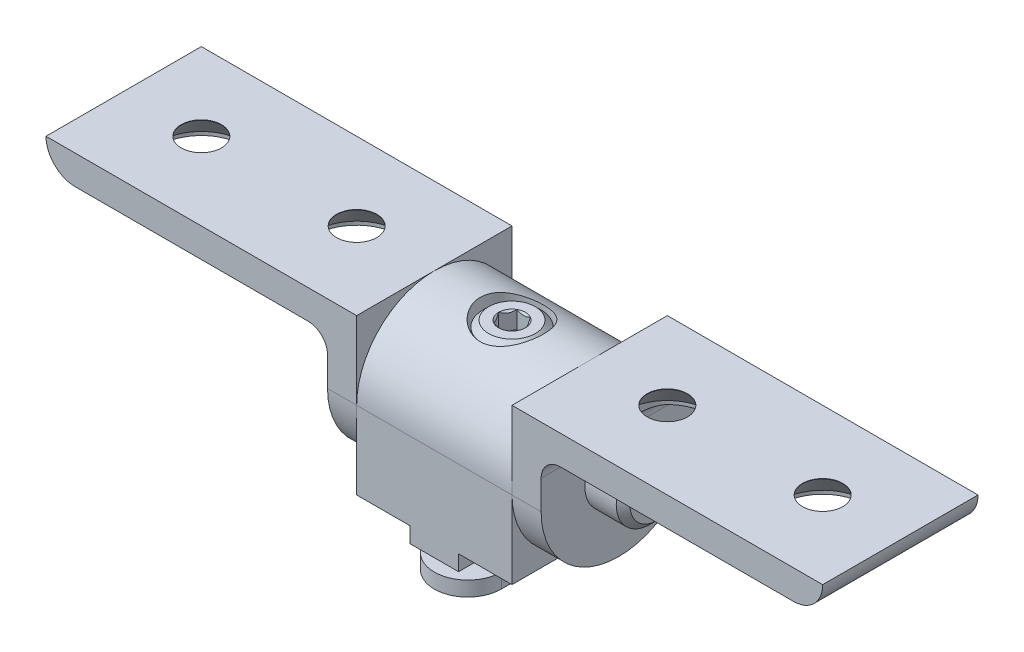
SolidWorks part; units mm, degrees
ref_plane "Front Plane" through (0, 0, 0) normal (0, 0, 1) x (1, 0, 0)
ref_plane "Top Plane" through (0, 0, 0) normal (0, 1, 0) x (1, 0, 0)
ref_plane "Right Plane" through (0, 0, 0) normal (1, 0, 0) x (0, 0, -1)
sketch "Sketch1" plane through (0, 0, 0) normal (1, 0, 0) x (0, 0, -1)
  line L0 (0, 0) -> (0, -6.985) construction
  line L2 (-12.7, 12.7) -> (-12.7, 0) construction
  line L3 (-12.7, 0) -> (12.7, 0) construction
  line L4 (12.7, 12.7) -> (12.7, 0) construction
  line L5 (-4.7625, 24.765) -> (4.7625, 24.765) construction
  line L7 (12.7, 0) -> (12.7, -2.54) construction
  line L12 (12.7, -2.54) -> (4.7752, -2.54) construction
  line L13 (-5.1911, 18.415) -> (5.1911, 18.415) construction
  line L14 (-3.2982, 12.7) -> (3.2982, 12.7) construction
  line L15 (0, 18.415) -> (0, 24.765) construction
  line L16 (-3.175, 19.5262) -> (-3.175, 18.415) construction
  line L17 (-3.175, 18.415) -> (-2.3501, 18.8912) construction
  line L18 (-2.3501, 18.8912) -> (-2.3501, 19.05) construction
  line L19 (-2.3501, 19.05) -> (-3.175, 19.5262) construction
  line L20 (-2.3501, 18.9706) -> (-3.175, 18.9706) construction
  line L21 (-3.175, 19.5262) -> (-3.3125, 19.6056) construction
  line L22 (-3.3125, 19.6056) -> (-3.3125, 18.3356) construction
  line L23 (-3.3125, 18.3356) -> (-3.175, 18.415) construction
  line L24 (-2.7626, 19.2881) -> (-2.7626, 18.6531) construction
  line L25 (-3.175, 18.9706) -> (-3.3125, 18.9706) construction
  circle A1 centre (0, 12.7) radius 3.175 construction
  circle A2 centre (0, 12.7) radius 12.7 construction
  point P6 (0, 25.4)
  point P11 (0, 18.415)
  point P20 (0, -6.985)
  point P24 (0, 18.415)
  point P25 (0, 12.7)
  point P45 (3.175, 12.7)
  dimension "D3" = 60
  dimension "D4" = 0.635
  dimension "D5" = 0.1588
sketch "Sketch6" plane through (0, 0, 0) normal (0, 0, 1) x (1, 0, 0)
  line L1 (12.7, 0) -> (-12.7, 0) construction
  line L5 (-23.7109, 18.2563) -> (-17.4625, 18.2563) construction
  line L6 (-12.7, 0) -> (-63.5, 0) construction
  line L7 (-17.4625, 18.2563) -> (-17.4625, 17.4625) construction
  line L10 (-17.4625, 17.4625) -> (-12.7, 17.4625) construction
  line L11 (-12.7, 17.4625) -> (-12.7, 15.875) construction
  line L12 (-12.7, 15.875) -> (-6.35, 15.875) construction
  line L13 (-6.35, 15.875) -> (-6.35, 9.525) construction
  line L14 (-6.35, 9.525) -> (-12.7, 9.525) construction
  line L15 (-12.7, 9.525) -> (-12.7, 7.9375) construction
  line L16 (-12.7, 7.9375) -> (-17.4625, 7.9375) construction
  line L19 (-17.4625, 7.9375) -> (-17.4625, 7.1438) construction
  line L20 (-17.4625, 7.1438) -> (-23.7109, 7.1438) construction
  line L21 (-23.7109, 7.1438) -> (-23.7109, 18.2563) construction
  line L22 (-23.7109, 12.7) -> (-6.35, 12.7) construction
  line L23 (12.7, 0) -> (63.5, 0) construction
  line L24 (-63.5, 0) -> (-63.5, 4.7625) construction
  line L25 (63.5, 0) -> (63.5, 4.7625) construction
  point P12 (0, 0)
  point P18 (-25.4, 0)
  point P23 (-50.8, 0)
  point P25 (-38.1, 0)
  dimension "D6" = 6.35
  dimension "D1" = 12.7
sketch "Sketch2" plane through (0, 0, 0) normal (1, 0, 0) x (0, 0, -1)
  line L0 (12.7, 12.7) -> (12.7, 0) construction
  line L1 (-12.7, 0) -> (12.7, 0) construction
  line L2 (-12.7, 12.7) -> (-12.7, 0) construction
  line L3 (12.7, 12.7) -> (12.7, 0)
  line L4 (-12.7, 0) -> (12.7, 0)
  line L5 (-12.7, 12.7) -> (-12.7, 0)
  circle A0 centre (0, 12.7) radius 3.175 construction
  circle A2 centre (0, 12.7) radius 3.175
  arc A4 (-12.7, 12.7) -> (12.7, 12.7) centre (0, 12.7) cw
extrude "Boss-Extrude1" add sketch "Sketch2" along normal mid plane 25.4 contours A4 L5 L4 L3 A2
sketch "Sketch3" plane through (0, 0, 0) normal (1, 0, 0) x (0, 0, -1)
  line L11 (4.7752, -2.54) -> (12.7, -2.54)
  line L12 (4.7752, -2.54) -> (4.7752, 0)
  line L13 (4.7752, 0) -> (12.7, 0)
  line L14 (12.7, -2.54) -> (12.7, 0)
  line L15 (-12.7, 0) -> (-4.7752, 0)
  line L16 (-12.7, 0) -> (-12.7, -2.54)
  line L17 (-12.7, -2.54) -> (-4.7752, -2.54)
  line L18 (-4.7752, 0) -> (-4.7752, -2.54)
  dimension "D1" = 2.54
  dimension "D2" = 7.9248
extrude "Boss-Extrude2" add sketch "Sketch3" along normal mid plane 7.9248
sketch "Sketch4" plane through (0, 0, 0) normal (0, 0, 1) x (1, 0, 0)
  line L0 (12.7, 12.7) -> (12.7, 0) construction
  line L9 (12.7, 0) -> (3.9624, 0) construction
  line L11 (4.7752, -2.54) -> (12.7, -2.54)
  line L12 (4.7752, -2.54) -> (4.7752, 0)
  line L13 (4.7752, 0) -> (12.7, 0)
  line L14 (12.7, -2.54) -> (12.7, 0)
  line L15 (-12.7, 0) -> (-4.7752, 0)
  line L16 (-12.7, 0) -> (-12.7, -2.54)
  line L17 (-12.7, -2.54) -> (-4.7752, -2.54)
  line L18 (-4.7752, 0) -> (-4.7752, -2.54)
  dimension "D1" = 7.9248
  dimension "D2" = 2.54
extrude "Boss-Extrude3" [suppressed] add sketch "Sketch4" along normal mid plane 7.9248
sketch "Sketch22" plane through (0, 0, 0) normal (0, 0, 1) x (1, 0, 0)
  line L6 (-12.7, 0) -> (-12.7, 25.4)
  line L7 (-12.7, 25.4) -> (-63.5, 25.4)
  line L9 (-58.7375, 20.6375) -> (-20.6375, 20.6375)
  line L10 (-17.4625, 17.4625) -> (-17.4625, 0)
  line L11 (-12.7, 0) -> (-63.5, 0) construction
  line L12 (-17.4625, 0) -> (-12.7, 0)
  line L13 (-20.6375, 20.6375) -> (-20.6375, 25.4) construction
  line L14 (-17.4625, 17.4625) -> (-12.7, 17.4625) construction
  line L15 (-63.5, 0) -> (-63.5, 4.7625) construction
  arc A2 (-17.4625, 17.4625) -> (-20.6375, 20.6375) centre (-20.6375, 17.4625) ccw
  arc A3 (-58.7375, 20.6375) -> (-63.5, 25.4) centre (-58.7375, 25.4) cw
  dimension "D1" = 3.175
extrude "Boss-Extrude8" add sketch "Sketch22" along normal mid plane 25.4 separate body
sketch "Sketch23" plane through (-17.4625, 0, 0) normal (-1, 0, 0) x (0, 0, 1)
  line L3 (12.7, 12.7) -> (12.7, 0) construction
  line L4 (-12.7, 12.7) -> (-12.7, -6.985)
  line L5 (-12.7, -6.985) -> (12.7, -6.985)
  line L6 (12.7, -6.985) -> (12.7, 12.7)
  circle A1 centre (0, 12.7) radius 4.7625
  arc A2 (-12.7, 12.7) -> (12.7, 12.7) centre (0, 12.7) ccw
  circle A3 centre (0, 12.7) radius 12.7 construction
extrude "Cut-Extrude7" cut sketch "Sketch23" against normal through all
sketch "Sketch24" plane through (0, 0, 0) normal (0, 0, 1) x (1, 0, 0)
  line L0 (-50.8, 0) -> (-50.8, 25.4) construction
  line L11 (-12.7, 25.4) -> (-63.5, 25.4) construction
  line L12 (-54.0982, 25.4) -> (-54.0982, 25.3319)
  line L13 (-54.0982, 25.3319) -> (-57.6821, 21.209)
  line L14 (-57.6821, 21.209) -> (-57.6821, 20.6375)
  line L15 (-58.7375, 20.6375) -> (-20.6375, 20.6375) construction
  line L16 (-57.6821, 20.6375) -> (-50.8, 20.6375) construction
  line L17 (-50.8, 20.6375) -> (-50.8, 25.4)
  line L18 (-50.8, 25.4) -> (-54.0982, 25.4)
  line L19 (-57.6821, 20.6375) -> (-57.6821, 12.7)
  line L20 (-57.6821, 12.7) -> (-50.8, 12.7)
  line L21 (-50.8, 12.7) -> (-50.8, 20.6375)
  line L22 (-23.7109, 12.7) -> (-6.35, 12.7) construction
  dimension "D1" = 49
  dimension "D2" = 6.5964
  dimension "D3" = 13.7643
  dimension "D4" = 0.5715
revolve "Cut-Revolve1" cut sketch "Sketch24" angle 360 about L0
pattern_linear "LPattern1" count 2 spacing 25.4 along (1, 0, 0) of "Cut-Revolve1"
sketch "Sketch8" plane through (0, 0, 0) normal (0, 0, 1) x (1, 0, 0)
  line L6 (-22.5996, 18.2563) -> (-17.4625, 18.2563)
  line L9 (-17.4625, 18.2563) -> (-17.4625, 17.4625)
  line L10 (-17.4625, 17.4625) -> (-12.7, 17.4625)
  line L11 (-12.7, 17.4625) -> (-12.7, 15.875)
  line L12 (-12.7, 15.875) -> (-6.35, 15.875)
  line L13 (-6.35, 15.875) -> (-6.35, 12.7)
  line L19 (-23.7109, 12.7) -> (-23.7109, 17.145)
  line L20 (-23.7109, 12.7) -> (-6.35, 12.7)
  line L21 (-23.7109, 12.7) -> (0, 12.7) construction
  line L22 (-23.7109, 17.145) -> (-22.5996, 18.2563)
  dimension "D1" = 45
  dimension "D2" = 1.1113
revolve "Revolve1" add sketch "Sketch8" angle 360 about L21
sketch "Sketch9" plane through (-23.7109, 0, 0) normal (-1, 0, 0) x (0, 0, 1)
  line L1 (0, 14.8997) -> (-1.905, 13.7999)
  line L2 (-1.905, 13.7999) -> (-1.905, 11.6001)
  line L3 (-1.905, 11.6001) -> (0, 10.5003)
  line L4 (0, 10.5003) -> (1.905, 11.6001)
  line L5 (1.905, 11.6001) -> (1.905, 13.7999)
  line L6 (1.905, 13.7999) -> (0, 14.8997)
  circle A0 centre (0, 12.7) radius 1.905 construction
extrude "Cut-Extrude1" cut sketch "Sketch9" against normal blind 2.8575
sketch "Sketch10" plane through (-23.7109, 0, 0) normal (-1, 0, 0) x (0, 0, 1)
  circle A0 centre (0, 12.7) radius 2.1997
extrude "Cut-Extrude2" cut sketch "Sketch10" against normal through all draft 45
mirror "Mirror2" about plane through (0, 0, 0) normal (1, 0, 0) of bodies 111 129 107 126
ref_plane "Plane2" through (0, 18.415, 0) normal (0, 1, 0) x (1, 0, 0)
sketch "Sketch12" plane through (0, 18.415, 0) normal (0, 1, 0) x (1, 0, 0)
  circle A0 centre (0, 0) radius 5.1911
extrude "Cut-Extrude3" cut sketch "Sketch12" along normal through all
sketch "Sketch13" plane through (0, 18.415, 0) normal (0, 1, 0) x (1, 0, 0)
  circle A0 centre (0, 0) radius 3.2982
extrude "Cut-Extrude4" cut sketch "Sketch13" against normal through all
ref_plane "Plane3" through (0, -6.985, 0) normal (0, 1, 0) x (1, 0, 0)
sketch "Sketch14" plane through (0, -6.985, 0) normal (0, 1, 0) x (1, 0, 0)
  line L0 (0, 7.2231) -> (0, -7.2231) construction
  line L1 (5.4769, 7.2231) -> (5.4769, -7.2231)
  line L2 (-5.4769, 7.2231) -> (-5.4769, -7.2231)
  arc A0 (5.4769, 7.2231) -> (-5.4769, 7.2231) centre (0, 7.2231) ccw
  arc A1 (-5.4769, -7.2231) -> (5.4769, -7.2231) centre (0, -7.2231) ccw
  circle A3 centre (0, 0) radius 3.175
  point P2 (0, 0)
  point P10 (0, -12.7)
  dimension "D1" = 6.35
  dimension "D2" = 2.3019
extrude "Boss-Extrude6" add sketch "Sketch14" along normal blind 2.413 separate body
sketch "Sketch16" plane through (0, 18.415, 0) normal (0, 1, 0) x (1, 0, 0)
  circle A0 centre (0, 0) radius 3.175
extrude "Boss-Extrude7" add sketch "Sketch16" against normal up to vertex (25.4 mm away) separate body up to point (0, -6.985, 0)
sketch "Sketch17" plane through (0, 18.415, 0) normal (0, 1, 0) x (1, 0, 0)
  circle A1 centre (0, 0) radius 3.175
  circle A2 centre (0, 0) radius 3.175
  dimension "D1" = 0
sketch "Sketch19" plane through (0, 0, 0) normal (1, 0, 0) x (0, 0, -1)
  line L0 (0, 18.415) -> (0, 24.765)
  line L1 (0, 18.415) -> (0, 24.765) construction
  line L2 (0, 24.765) -> (3.81, 24.765)
  line L3 (3.81, 24.765) -> (4.7625, 23.8125)
  line L4 (4.7625, 23.8125) -> (4.7625, 18.415)
  line L5 (-5.1911, 18.415) -> (5.1911, 18.415) construction
  line L6 (4.7625, 18.415) -> (0, 18.415)
  line L7 (0, 25.4) -> (0, 0) construction
  dimension "D1" = 45
  dimension "D2" = 0.9525
  dimension "D3" = 6.35
revolve "Revolve3" add sketch "Sketch19" angle 360 about L7
sketch "Sketch20" plane through (0, 24.765, 0) normal (0, 1, 0) x (1, 0, 0)
  line L1 (1.0999, 1.905) -> (-1.0999, 1.905)
  line L2 (-1.0999, 1.905) -> (-2.1997, 0)
  line L3 (-2.1997, 0) -> (-1.0999, -1.905)
  line L4 (-1.0999, -1.905) -> (1.0999, -1.905)
  line L5 (1.0999, -1.905) -> (2.1997, 0)
  line L6 (2.1997, 0) -> (1.0999, 1.905)
  circle A0 centre (0, 0) radius 1.905 construction
  dimension "D1" = 3.81
extrude "Cut-Extrude5" cut sketch "Sketch20" against normal blind 2.8575
sketch "Sketch21" plane through (0, 24.765, 0) normal (0, 1, 0) x (1, 0, 0)
  circle A0 centre (0, 0) radius 2.1997
extrude "Cut-Extrude6" cut sketch "Sketch21" against normal through all draft 45
curve "Helix/Spiral1" pitch 1.27 height 26.67 turns 21
sketch "Sketch18" plane through (0, 0, 0) normal (1, 0, 0) x (0, 0, -1)
  line L0 (-3.175, 19.5262) -> (-3.175, 18.415)
  line L1 (-3.175, 18.415) -> (-2.3501, 18.8912)
  line L2 (-2.3501, 18.8912) -> (-2.3501, 19.05)
  line L3 (-2.3501, 19.05) -> (-3.175, 19.5262)
sweep "Cut-Sweep1" cut profiles "Sketch18" path "Helix/Spiral1"
equation "\"D1@Boss-Extrude1\"=\"D@Sketch1\""
equation "\"D1@Boss-Extrude2\"=\"Tab Width@Sketch1\""
equation "\"D2@Sketch4\" = \"Tab Height@Sketch1\""
equation "\"D1@Sketch4\"=\"Tab Width@Sketch1\""
equation "\"D1@Boss-Extrude3\"=\"Tab Width@Sketch1\""
equation "\"D1@Sketch3\"=\"Tab Height@Sketch1\""
equation "\"D2@Sketch3\"=\"Tab Width@Sketch1\""
equation "\"D1@Cut-Extrude1\"=\"Hex Size@Sketch9\"*.75"
equation "\"Screw Clearence@Sketch1\"=\"Thread OD@Sketch1\"*1.0388"
equation "\"D1@Sketch14\"=\"Thread OD@Sketch1\""
equation "\"D4@Sketch1\"=\"Pitch@Sketch1\"/2"
equation "\"D5@Sketch1\"=\"Pitch@Sketch1\"/8"
equation "\"D4@Helix/Spiral1\"=\"Pitch@Sketch1\""
equation "\"D3@Helix/Spiral1\"=\"Thread Length@Sketch1\"+\"Pitch@Sketch1\""
equation "\"D2@Sketch19\"=\"Head Dia@Sketch1\"*.1"
equation "\"D3@Sketch19\"=\"Head Height@Sketch1\""
equation "\"D1@Sketch20\"=\"Hex Size@Sketch9\""
equation "\"D1@Cut-Extrude5\"=\"D1@Cut-Extrude1\""
equation "\"D2@Sketch8\" = \"Shoulder Head Dia@Sketch6\" * .1"
equation "\"Head Height@Sketch1\"=\"Thread OD@Sketch1\""
equation "\"D6@Sketch6\"=\"Thread OD@Sketch1\""
equation "\"Head Dia@Sketch1\"=\"Thread OD@Sketch1\"*1.5"
equation "\"Shoulder Head Dia@Sketch6\"=1.75*\"Thread OD@Sketch1\""
equation "\"C'Bore Dia@Sketch1\"=1.09*\"Head Dia@Sketch1\""
equation "\"Hex Size@Sketch9\"=\"Thread OD@Sketch1\"*.6"
equation "\"D1@Sketch6\" = .5 * \"C@Sketch6\""
equation "\"Pivot Width@Sketch6\"=\"D@Sketch1\""
equation "\"D1@Boss-Extrude8\"=\"D@Sketch1\""
equation "\"D3@LPattern1\"=\"C@Sketch6\""
equation "\"D2@Sketch24\"=\"Thread OD@Sketch1\"*1.0388"
equation "\"D3@Sketch24\"=\"Thread OD@Sketch1\"*2.1676"
equation "\"D4@Sketch24\"=.09*\"Thread OD@Sketch1\""
